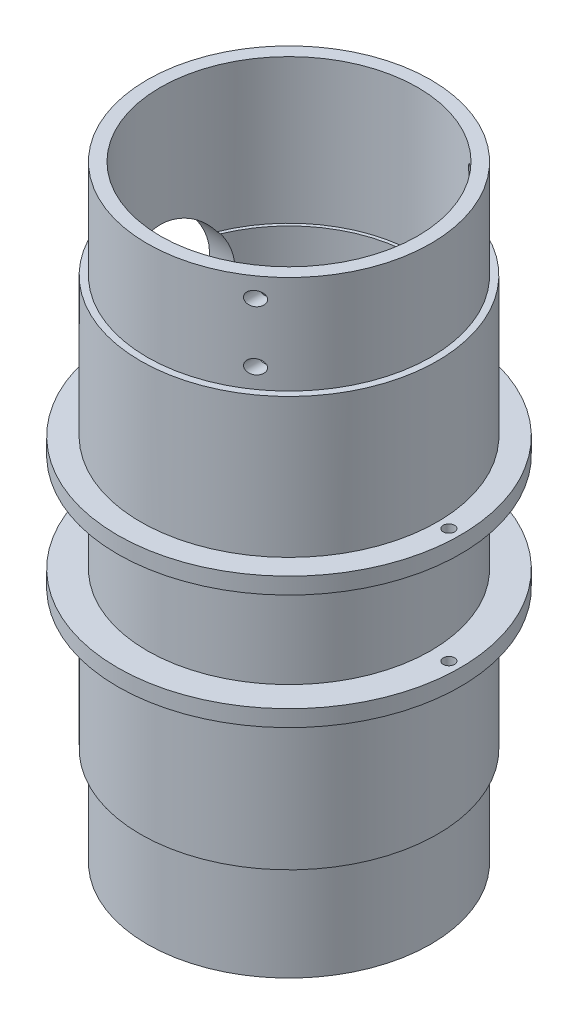
SolidWorks part; units mm, degrees
ref_plane "Front Plane" through (0, 0, 0) normal (0, 0, 1) x (1, 0, 0)
ref_plane "Top Plane" through (0, 0, 0) normal (0, 1, 0) x (1, 0, 0)
ref_plane "Right Plane" through (0, 0, 0) normal (1, 0, 0) x (0, 0, -1)
sketch "Sketch1" plane through (0, 0, 0) normal (0, 1, 0) x (1, 0, 0)
  line L0 (0, 38.25) -> (0, 45.25) construction
  circle A0 centre (0, 0) radius 38.25
  circle A1 centre (0, 0) radius 45.25
  dimension "D1" = 76.5
  dimension "D2" = 7
extrude "Boss-Extrude1" add sketch "Sketch1" along normal mid plane 185
sketch "Sketch2" plane through (0, -92.5, 0) normal (0, -1, 0) x (1, 0, 0)
  line L0 (0, 36.25) -> (0, 38.25) construction
  circle A0 centre (0, 0) radius 36.25
  circle A1 centre (0, 0) radius 38.25 construction
  circle A2 centre (0, 0) radius 38.25
  dimension "D1" = 2
extrude "Boss-Extrude2" add sketch "Sketch2" against normal blind 100 from offset 6.35 offset against normal yes
sketch "Sketch6" plane through (0, 92.5, 0) normal (0, 1, 0) x (1, 0, 0)
  line L0 (0, 38.25) -> (0, 39.25) construction
  circle A0 centre (0, 0) radius 39.25
  circle A1 centre (0, 0) radius 38.25 construction
  circle A2 centre (0, 0) radius 38.25
  dimension "D1" = 1
extrude "Cut-Extrude3" cut sketch "Sketch6" against normal blind 44
sketch "Sketch7" plane through (0, 0, 0) normal (1, 0, 0) x (0, 0, -1)
  line L0 (45.25, 92.5) -> (-45.25, 92.5) construction
  circle A0 centre (0, 38.75) radius 17.5
  dimension "D2" = 35
  dimension "D1" = 53.75
extrude "Cut-Extrude4" cut sketch "Sketch7" against normal through all
sketch "Sketch8" plane through (0, 92.5, 0) normal (0, 1, 0) x (1, 0, 0)
  line L0 (0, 43.25) -> (0, 45.25) construction
  circle A0 centre (0, 0) radius 45.25 construction
  circle A1 centre (0, 0) radius 45.25
  circle A2 centre (0, 0) radius 43.25
  dimension "D1" = 2
extrude "Cut-Extrude5" cut sketch "Sketch8" against normal blind 30
mirror "Mirror1" about plane through (0, 0, 0) normal (0, 1, 0) of "Cut-Extrude5"
sketch "Sketch9" plane through (0, 0, 0) normal (0, 1, 0) x (1, 0, 0)
  circle A1 centre (0, 0) radius 43.25
  circle A2 centre (0, 0) radius 43.25
  circle A3 centre (0, 0) radius 45.25
  circle A4 centre (0, 0) radius 45.25
  dimension "D1" = 0
  dimension "D2" = 0
extrude "Cut-Extrude6" cut sketch "Sketch9" against normal mid plane 30
ref_plane "Plane1" through (0, 15, 0) normal (0, -1, 0) x (-1, 0, 0)
sketch "Sketch10" plane through (0, 15, 0) normal (0, -1, 0) x (-1, 0, 0)
  circle A0 centre (0, 0) radius 52.25
  circle A1 centre (0, 0) radius 43.25
  circle A2 centre (-48.75, 0) radius 1.75
  dimension "D1" = 48.75
  dimension "D2" = 3.5
extrude "Boss-Extrude3" add sketch "Sketch10" against normal blind 5
ref_plane "Plane2" through (0, 0, 0) normal (0, 1, 0) x (1, 0, 0)
mirror "Mirror2" about plane through (0, 0, 0) normal (0, 1, 0) of "Boss-Extrude3"
hole_wizard "CBORE for M4 SHCS1" positions "Sketch15" profile "Sketch16" counterbore size "M4" standard "ANSI Metric"
sketch "Sketch15" plane through (401.677, -407.2242, 50.0506) normal (0, 0, 1) x (0.1676, 0.9859, 0)
  line L0 (405.8768, 451.0689) -> (423.6223, 454.0852) construction
  line L2 (414.7496, 452.577) -> (416.4253, 442.7184) construction
  circle A0 centre (405.8768, 451.0689) radius 2.25
  circle A1 centre (423.6223, 454.0852) radius 2.25
  point P0 (405.8768, 451.0689)
  point P2 (423.6223, 454.0852)
sketch "Sketch16" plane through (25, 68.5, 50.0506) normal (1, 0, 0) x (0, -1, 0)
  line L0 (0, 0) -> (0, 101.393)
  line L1 (0, 101.393) -> (2.15, 100.1012)
  line L2 (2.15, 100.1012) -> (2.15, 4)
  line L3 (2.15, 4) -> (4, 4)
  line L4 (4, 4) -> (4, 0)
  line L5 (4, 0) -> (0, 0)
  line L6 (0, 101.393) -> (-2.15, 100.1012) construction
  line L7 (0, -6.35) -> (0, 107.95) construction
  dimension "Hole Dia." = 4.3
  dimension "Hole Depth" = 100.1012
  dimension "C'Bore Dia." = 8
  dimension "C'Bore Depth" = 4
  dimension "Drill Angle" = 118
